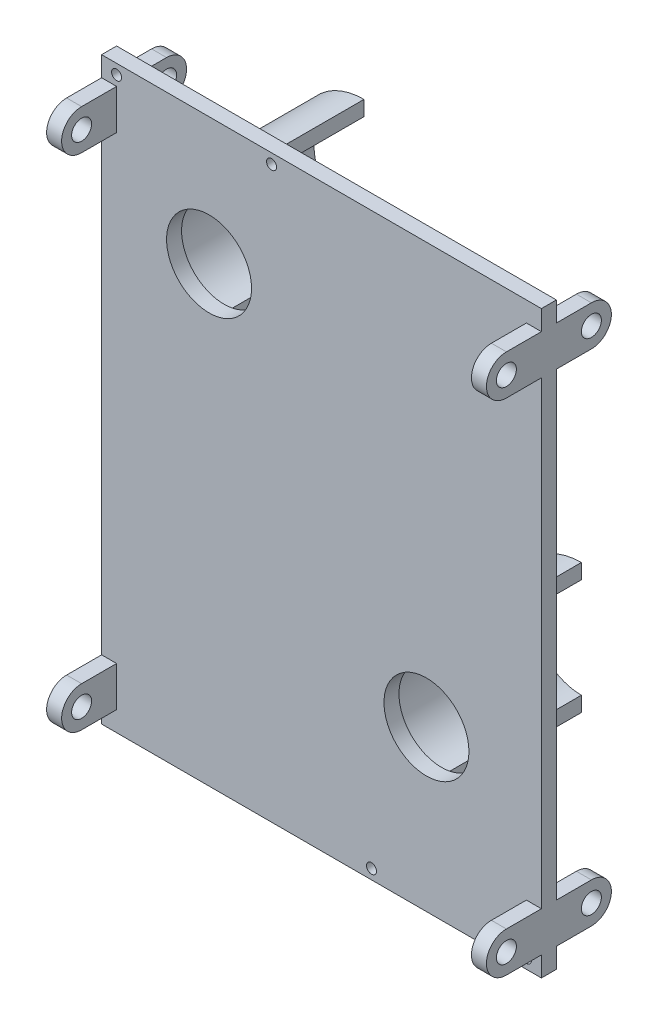
SolidWorks part; units mm, degrees
material "2024-T4"
ref_plane "Front Plane" through (0, 0, 0) normal (0, 0, 1) x (1, 0, 0)
ref_plane "Top Plane" through (0, 0, 0) normal (0, 1, 0) x (1, 0, 0)
ref_plane "Right Plane" through (0, 0, 0) normal (1, 0, 0) x (0, 0, -1)
sketch "Sketch1" plane through (0, 0, 0) normal (0, 0, 1) x (1, 0, 0)
  line L1 (-44, -58) -> (44, -58)
  line L2 (-44, -58) -> (-44, 58)
  line L3 (-44, 58) -> (44, 58)
  line L4 (44, -58) -> (44, 58)
  line L5 (-44, -58) -> (44, 58) construction
  line L6 (-44, 58) -> (44, -58) construction
  circle A0 centre (-22.8181, 25.0296) radius 20 construction
  circle A1 centre (24.0245, 19.8034) radius 20 construction
  point P0 (0, 0)
  dimension "D3" = 40
  dimension "D1" = 88
  dimension "D2" = 116
extrude "Boss-Extrude1" add sketch "Sketch1" along normal blind 3 contours L3 L4 L1 L2
sketch "Sketch2" plane through (0, 0, 3) normal (0, 0, 1) x (1, 0, 0)
  line L0 (-44, -58) -> (-44, 58) construction
  line L1 (-44, 58) -> (44, 58) construction
  line L2 (44, 0) -> (-44, 0) construction
  line L3 (44, -58) -> (44, 58) construction
  line L4 (-44, -58) -> (44, -58) construction
  circle A0 centre (-22.5, 32.5) radius 20 construction
  circle A1 centre (21, -26) radius 20 construction
  circle A2 centre (-22.5, 32.5) radius 8.5
  circle A3 centre (21, -26) radius 8.5
  dimension "D2" = 40
  dimension "D6" = 17
  dimension "D4" = 26
  dimension "D5" = 32.5
  dimension "D3" = 23
  dimension "D1" = 43.5
  dimension "D7" = 25.5
  dimension "D8" = 32
extrude "Cut-Extrude1" cut sketch "Sketch2" against normal through all
sketch "Sketch4" plane through (-44, 0, 0) normal (-1, 0, 0) x (0, 0, 1)
  line L0 (0, 0) -> (10.9251, 0) construction
  line L1 (0, 58) -> (0, 50) construction
  line L2 (0, -58) -> (0, 58) construction
  line L3 (0, 50) -> (-7, 50) construction
  line L4 (-7, 54) -> (0, 54)
  line L5 (0, 54) -> (0, 46)
  line L6 (0, 46) -> (-7, 46)
  line L7 (0, -50) -> (-7, -50) construction
  line L8 (0, -58) -> (0, -50) construction
  line L9 (0, -46) -> (-7, -46)
  line L10 (0, -54) -> (0, -46)
  line L11 (-7, -54) -> (0, -54)
  line L12 (1.5, -58) -> (1.5, -62.9921) construction
  line L13 (3, -58) -> (0, -58) construction
  line L14 (3, 46) -> (10, 46)
  line L15 (3, 54) -> (3, 46)
  line L16 (10, 54) -> (3, 54)
  line L17 (10, -54) -> (3, -54)
  line L18 (3, -54) -> (3, -46)
  line L19 (3, -46) -> (10, -46)
  circle A0 centre (-7, 50) radius 2
  arc A1 (-7, 54) -> (-7, 46) centre (-7, 50) ccw
  arc A2 (-7, -54) -> (-7, -46) centre (-7, -50) cw
  circle A3 centre (-7, -50) radius 2
  circle A4 centre (10, 50) radius 2
  arc A5 (10, 54) -> (10, 46) centre (10, 50) cw
  circle A6 centre (10, -50) radius 2
  arc A7 (10, -54) -> (10, -46) centre (10, -50) ccw
  dimension "D3" = 8
  dimension "D4" = 4
  dimension "D1" = 7
  dimension "D2" = 8
extrude "Boss-Extrude3" add sketch "Sketch4" against normal blind 3
sketch "Sketch6" plane through (0, 0, 3) normal (0, 0, 1) x (1, 0, 0)
  line L0 (-44, 58) -> (-44, 54) construction
  line L1 (-44, 56) -> (-41, 56) construction
  line L2 (-44, 58) -> (-7, 58) construction
  line L3 (44, -58) -> (44, -54) construction
  line L4 (44, -58) -> (44, 58) construction
  line L5 (44, -56) -> (41, -56) construction
  line L6 (41, -56) -> (10, -56) construction
  circle A0 centre (-41, 56) radius 1
  circle A1 centre (-10, 56) radius 1
  circle A2 centre (41, -56) radius 1
  circle A3 centre (10, -56) radius 1
  dimension "D2" = 2
  dimension "D6" = 2
  dimension "D10" = 2
  dimension "D11" = 2
  dimension "D1" = 4
  dimension "D3" = 3
  dimension "D4" = 37
  dimension "D5" = 3
  dimension "D7" = 3
  dimension "D8" = 4
  dimension "D9" = 31
extrude "Cut-Extrude2" cut sketch "Sketch6" against normal blind 10
sketch "Sketch5" plane through (0, 0, 0) normal (0, 0, -1) x (-1, 0, 0)
  line L0 (22.5, 32.5) -> (22.5, 45.5) construction
  line L5 (-21, -26) -> (-21, -13) construction
  line L10 (22.5, 32.5) -> (32.5, 32.5) construction
  line L15 (22.5, 42.5) -> (22.5, 45.5)
  line L16 (22.5, 22.5) -> (22.5, 19.5)
  line L17 (-21, -16) -> (-21, -13)
  line L18 (-21, -36) -> (-21, -39)
  arc A0 (22.5, 22.5) -> (22.5, 42.5) centre (22.5, 32.5) ccw
  arc A1 (22.5, 19.5) -> (22.5, 45.5) centre (22.5, 32.5) ccw
  arc A2 (-21, -36) -> (-21, -16) centre (-21, -26) ccw
  arc A3 (-21, -39) -> (-21, -13) centre (-21, -26) ccw
  point P9 (22.5, 42.5)
  point P20 (-21, -16)
  point P26 (35.5, 32.5)
  dimension "D1" = 20
  dimension "D2" = 3
  dimension "D4" = 3
  dimension "D5" = 20
extrude "Boss-Extrude4" add sketch "Sketch5" along normal blind 28 contours L16 A1 L15 A0 | A3 L17 A2 L18 region at (-22.7907, 44, 0)
mirror "Mirror1" about plane through (0, 0, 0) normal (1, 0, 0) of "Boss-Extrude3"
mirror "Mirror2" [suppressed] of bodies 107
delete or keep bodies "Body-Delete/Keep 1" [suppressed] type delete bodies bodies 107
equation "\"mini-flipper-shaft-diameter\"= 26mm"
equation "\"mini-shaft-ring-groove-diam\"= 7.8mm"
equation "\"mini-shaft-ring-groove-width\"= 1mm"
equation "\"dtCoverPlate-DistFrom-GearCent\"= 73mm"
equation "\"wormGearShaft-L\"= \"dtCoverPlate-DistFrom-GearCent\" - 27.75 + 3.75"
equation "\"wormGearShaft-Dsmall\"= 6mm"
equation "\"wormGearShaft-Dworm\"= 12mm"
equation "\"wormL-D\" = 12mm"
equation "\"wormR-D\" = 15mm"
equation "\"wormGearL-D\" = 40mm"
equation "\"wormGearR-D\" = 50mm"
equation "\"D5@Sketch2\"=\"wormGearR-D\"/2 + \"wormR-D\"/2"
equation "\"D4@Sketch2\"=\"wormGearL-D\"/2 + \"wormL-D\"/2"
